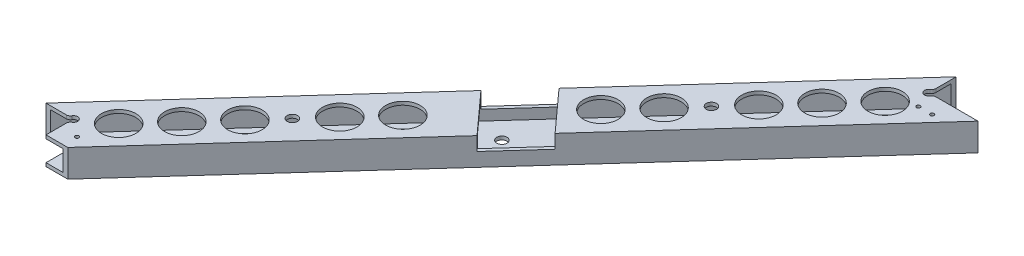
SolidWorks part; units mm, degrees
material "6061-T6 (SS)"
ref_plane "Front Plane" through (0, 0, 0) normal (0, 0, 1) x (1, 0, 0)
ref_plane "Top Plane" through (0, 0, 0) normal (0, 1, 0) x (1, 0, 0)
ref_plane "Right Plane" through (0, 0, 0) normal (1, 0, 0) x (0, 0, -1)
sketch "Sketch1" plane through (0, 0, 0) normal (0, 1, 0) x (1, 0, 0)
  line L0 (186.9237, 246.0625) -> (224.5957, 211.9823) construction
  line L1 (386.5474, 441.325) -> (432.072, 441.325)
  line L2 (12.7, 25.4) -> (12.7, -22.2456)
  line L7 (432.072, 441.325) -> (12.7, -22.2456)
  line L9 (-12.7, 25.4) -> (386.5474, 466.725)
  line L11 (12.7, -25.4) -> (-12.7, -25.4) construction
  line L12 (12.7, -25.4) -> (12.7, 25.4) construction
  line L13 (12.7, 25.4) -> (-12.7, 25.4)
  line L14 (-12.7, -25.4) -> (-12.7, 25.4) construction
  line L15 (12.7, -25.4) -> (-12.7, 25.4) construction
  line L16 (12.7, 25.4) -> (-12.7, -25.4) construction
  line L17 (386.5474, 466.725) -> (437.3474, 466.725) construction
  line L18 (386.5474, 466.725) -> (386.5474, 441.325)
  line L19 (386.5474, 441.325) -> (437.3474, 441.325) construction
  line L20 (437.3474, 466.725) -> (437.3474, 441.325) construction
  line L21 (386.5474, 466.725) -> (437.3474, 441.325) construction
  line L22 (386.5474, 441.325) -> (437.3474, 466.725) construction
  point P14 (0, 0)
  point P15 (0, 0)
  point P21 (411.9474, 454.025)
  dimension "D1" = 454.025
  dimension "D2" = 411.9474
  dimension "D3" = 50.8
  dimension "D4" = 50.8
  dimension "D5" = 25.4
extrude "Boss-Extrude1" add sketch "Sketch1" along normal blind 25.4
sketch "Sketch2" plane through (0, 25.4, 0) normal (0, 1, 0) x (1, 0, 0)
  line L0 (-12.7, 25.4) -> (-12.7, 50025.4) construction
  line L1 (437.3474, 466.725) -> (437.3474, 50466.725) construction
  line L2 (437.3474, 466.725) -> (-12.7, 466.725) construction
  line L3 (212.3237, 466.725) -> (212.3237, -49533.275) construction
  line L4 (386.5474, 466.725) -> (-12.7, 25.4) construction
  line L5 (12.7, -22.2456) -> (432.072, 441.325) construction
  line L6 (38.1, 466.725) -> (437.3474, 25.4) construction
  line L7 (411.9474, -22.2456) -> (-7.4246, 441.325) construction
  line L8 (212.3237, 274.1395) -> (246.5751, 236.2782)
  line L9 (246.5751, 236.2782) -> (212.3237, 198.4169)
  line L10 (212.3237, 198.4169) -> (178.0723, 236.2782)
  line L11 (178.0723, 236.2782) -> (212.3237, 274.1395)
  point P10 (212.3237, 466.725)
extrude "Cut-Extrude1" cut sketch "Sketch2" against normal blind 12.7
ref_axis "Axis1" through (12.7, 25.4, 22.2456) along (0.6709, 0, -0.7416)
ref_plane "Plane1" through (-5.3513, 0, 5.9153) normal (0.6709, 0, -0.7416) x (-0.7416, 0, -0.6709)
sketch "Sketch3" plane through (-5.3513, 0, 5.9153) normal (0.6709, 0, -0.7416) x (-0.7416, 0, -0.6709)
  line L0 (23.2831, 22.225) -> (23.2831, 25.4)
  line L1 (-24.3419, 0) -> (26.4581, 0) construction
  line L2 (-24.3419, 0) -> (-24.3419, 25.4) construction
  line L3 (-24.3419, 25.4) -> (26.4581, 25.4) construction
  line L4 (26.4581, 0) -> (26.4581, 25.4) construction
  line L5 (-24.3419, 0) -> (26.4581, 25.4) construction
  line L6 (-24.3419, 25.4) -> (26.4581, 0) construction
  line L7 (23.2831, 3.175) -> (-21.1669, 3.175)
  line L8 (23.2831, 3.175) -> (23.2831, 22.225)
  line L9 (23.2831, 22.225) -> (-21.1669, 22.225)
  line L10 (-21.1669, 3.175) -> (-21.1669, 22.225)
  line L11 (23.2831, 3.175) -> (-21.1669, 22.225) construction
  line L12 (23.2831, 22.225) -> (-21.1669, 3.175) construction
  line L13 (23.2831, 22.225) -> (26.4581, 22.225)
  point P0 (1.0581, 12.7)
  point P6 (1.0581, 12.7)
  dimension "D1" = 3.175
extrude "Cut-Extrude2" cut sketch "Sketch3" along normal through all contours L10 L7 L8 L9 region at (-6.136, 12.7, 5.2055)
hole_wizard "3/8 (0.375) Diameter Hole1" positions "Sketch5" profile "Sketch4" hole size "3/8" standard "ANSI Inch" end condition through all
sketch "Sketch5" plane through (0, 25.4, 0) normal (0, 1, 0) x (1, 0, 0)
  line L0 (82.6861, 130.8391) -> (120.3581, 96.7589)
  line L1 (178.0723, 236.2782) -> (-12.7, 25.4) construction
  line L5 (51.6025, 58.6182) -> (33595.1141, 37137.3565) construction
  line L7 (12.7, -22.2456) -> (212.3237, 198.4169) construction
  line L8 (12.7, 15.6157) -> (397.8206, 441.325) construction
  line L10 (432.072, 441.325) -> (386.5474, 441.325) construction
  line L11 (12.7, 25.4) -> (12.7, -22.2456) construction
  line L12 (113.3472, 126.8703) -> (205.2603, 228.4703)
  line L13 (205.2603, 228.4703) -> (297.1734, 330.0703)
  point P0 (113.3472, 126.8703)
  point P2 (297.1734, 330.0703)
  point P16 (101.5221, 113.799)
  point P42 (205.2603, 228.4703)
  dimension "D1" = 203.2
sketch "Sketch4" plane through (113.3472, 25.4, -126.8703) normal (1, 0, 0) x (0, 0, 1)
  line L0 (0, 0) -> (0, 25.4)
  line L1 (0, 25.4) -> (4.7625, 25.4)
  line L2 (4.7625, 25.4) -> (4.7625, 0)
  line L5 (4.7625, 0) -> (0, 0)
  line L11 (0, -6.35) -> (0, 107.95) construction
  dimension "Thru Hole Dia." = 9.525
  dimension "Thru Hole Depth" = 25.4
sketch "Sketch6" plane through (0, 25.4, 0) normal (0, 1, 0) x (1, 0, 0)
  line L0 (12.7, -22.2456) -> (32.8246, 0)
  line L1 (12.7, -22.2456) -> (212.3237, 198.4169) construction
  line L2 (32.8246, 0) -> (12.7, 0)
  line L3 (12.7, 25.4) -> (12.7, -22.2456) construction
  line L4 (12.7, 0) -> (12.7, -22.2456)
  line L5 (-12.7, 25.4) -> (12.7, 25.4) construction
  point P5 (0, 25.4)
  dimension "D1" = 25.4
extrude "Cut-Extrude3" cut sketch "Sketch6" against normal through all
hole_wizard "#8-32 Tapped Hole1" positions "Sketch8" profile "Sketch7" tap size "#8-32" standard "ANSI Inch" end condition through all
sketch "Sketch8" plane through (0, 25.4, 0) normal (0, 1, 0) x (1, 0, 0)
  line L0 (28.575, 12.7) -> (28.575, 50012.7) construction
  line L1 (25.7498, 12.7) -> (-49974.2502, 12.7) construction
  line L2 (-12.7, 25.4) -> (12.7, 25.4) construction
  line L3 (12.7, 25.4) -> (12.7, 0) construction
  point P0 (28.575, 12.7)
  dimension "D1" = 12.7
  dimension "D2" = 15.875
sketch "Sketch7" plane through (28.575, 25.4, -12.7) normal (1, 0, 0) x (0, 0, 1)
  line L0 (0, 0) -> (0, 25.4)
  line L1 (0, 25.4) -> (1.7272, 25.4)
  line L2 (1.7272, 25.4) -> (1.7272, 0)
  line L5 (1.7272, 0) -> (0, 0)
  line L11 (0, -6.35) -> (0, 107.95) construction
  dimension "Thru Tap Drill Dia." = 3.4544
  dimension "Thru Tap Drill Depth" = 25.4
cosmetic thread "Hole Thread1" parameters "D2"=4.1656
sketch "Sketch9" plane through (0, 25.4, 0) normal (0, 1, 0) x (1, 0, 0)
  circle A0 centre (12.7, 25.4) radius 3.81
  circle A1 centre (386.5474, 441.325) radius 3.81
  dimension "D1" = 7.62
extrude "Cut-Extrude4" cut sketch "Sketch9" against normal through all
fillet "Fillet1" radius 3.81 8 edges at (12.7, 1.5875, -21.59) (12.7, 23.8125, -21.59) (8.89, 1.5875, -25.4) (8.89, 23.8125, -25.4) (390.3574, 23.8125, -441.325) (390.3574, 1.5875, -441.325) (386.5474, 1.5875, -445.135) (386.5474, 23.8125, -445.135)
hole_wizard "#8-32 Tapped Hole2" positions "Sketch11" profile "Sketch10" tap size "#8-32" standard "ANSI Inch" end condition through all
sketch "Sketch11" plane through (0, 25.4, 0) normal (0, 1, 0) x (1, 0, 0)
  line L0 (386.5474, 441.325) -> (386.5474, 50441.325) construction
  line L1 (386.5474, 441.325) -> (50386.5474, 441.325) construction
  line L3 (386.5474, 425.45) -> (437.3474, 425.45) construction
  line L5 (411.9474, 428.1635) -> (411.9474, 50428.1635) construction
  point P0 (392.8974, 425.45)
  point P2 (405.5974, 425.45)
  point P22 (411.9474, 425.45)
  dimension "D1" = 50.8
  dimension "D2" = 15.875
  dimension "D3" = 19.05
  dimension "D4" = 6.35
sketch "Sketch10" plane through (392.8974, 25.4, -425.45) normal (1, 0, 0) x (0, 0, 1)
  line L0 (0, 0) -> (0, 25.4)
  line L1 (0, 25.4) -> (1.7272, 25.4)
  line L2 (1.7272, 25.4) -> (1.7272, 0)
  line L5 (1.7272, 0) -> (0, 0)
  line L11 (0, -6.35) -> (0, 107.95) construction
  dimension "Thru Tap Drill Dia." = 3.4544
  dimension "Thru Tap Drill Depth" = 25.4
cosmetic thread "Hole Thread2" parameters "D2"=4.1656
cosmetic thread "Hole Thread3" parameters "D2"=4.1656
sketch "Sketch12" plane through (0, 25.4, 0) normal (0, 1, 0) x (1, 0, 0)
  line L0 (82.6861, 130.8391) -> (120.3581, 96.7589) construction
  line L1 (178.0723, 236.2782) -> (-12.7, 25.4) construction
  line L2 (32.8246, 0) -> (212.3237, 198.4169) construction
  line L3 (101.5221, 113.799) -> (-33441.9895, -36964.9393) construction
  line L4 (19.0281, 24.813) -> (-35905.3477, 32524.0233) construction
  line L5 (113.3472, 126.8703) -> (-36965.391, 33670.3819) construction
  line L6 (229.4494, 255.2088) -> (195.198, 217.3476) construction
  line L7 (246.5751, 236.2782) -> (212.3237, 274.1395) construction
  line L8 (178.0723, 236.2782) -> (212.3237, 198.4169) construction
  line L9 (205.2603, 228.4703) -> (-32304.5907, 29638.7096) construction
  circle A0 centre (37.1638, 42.6578) radius 15.875
  arc A1 (14.605, 22.1004) -> (9.4004, 27.305) centre (12.7, 25.4) ccw construction
  circle A2 centre (64.854, 73.2663) radius 15.875
  circle A3 centre (92.5442, 103.8748) radius 15.875
  circle A4 centre (134.1503, 149.8659) radius 15.875
  circle A5 centre (161.8404, 180.4744) radius 15.875
  circle A6 centre (373.3568, 414.2829) radius 15.875
  circle A7 centre (345.6666, 383.6744) radius 15.875
  circle A8 centre (317.9764, 353.0659) radius 15.875
  circle A9 centre (248.6801, 276.4663) radius 15.875
  circle A10 centre (276.3703, 307.0748) radius 15.875
  point P8 (101.5221, 113.799)
  point P35 (212.3237, 236.2782)
  point P36 (205.2603, 228.4703)
  dimension "D1" = 9.525
  dimension "D3" = 31.75
  dimension "D2" = 9.525
  dimension "D5" = 41.275
  dimension "D4" = 3
extrude "Cut-Extrude5" cut sketch "Sketch12" against normal through all
